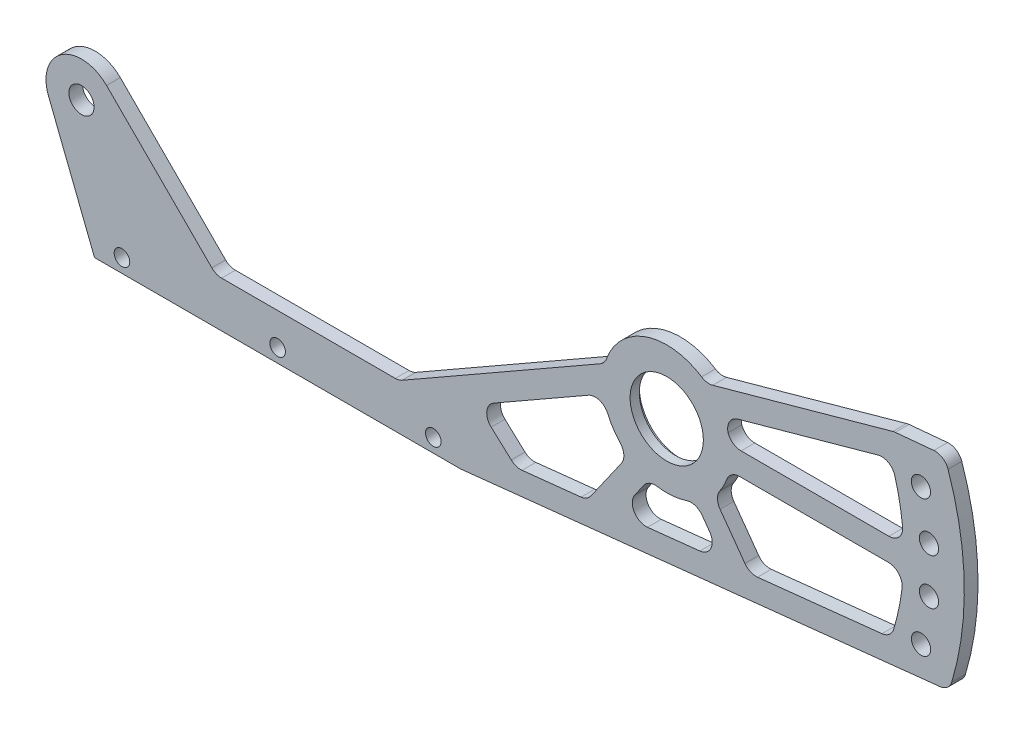
SolidWorks part; units mm, degrees
ref_plane "Спереди" through (0, 0, 0) normal (0, 0, 1) x (1, 0, 0)
ref_plane "Сверху" through (0, 0, 0) normal (0, 1, 0) x (1, 0, 0)
ref_plane "Справа" through (0, 0, 0) normal (1, 0, 0) x (0, 0, -1)
sketch "Эскиз1" plane through (0, 0, 0) normal (0, 0, 1) x (1, 0, 0)
  line L0 (0, 0) -> (80, 0)
  line L1 (80, 0) -> (186.6474, 11.3941)
  line L3 (185.6418, 55.4002) -> (29.8179, 40.9591)
  line L4 (29.8179, 40.9591) -> (0, 40.9591)
  line L5 (0, 40.9591) -> (0, 0)
  line L6 (125, 71.1667) -> (125, -25.6191) construction
  line L7 (154.8278, 32) -> (80, 32) construction
  circle A0 centre (125, 32) radius 8
  arc A1 (186.6474, 11.3941) -> (185.6418, 55.4002) centre (125, 32) ccw
  dimension "D4" = 16
  dimension "D3" = 130
  dimension "D1" = 80
  dimension "D2" = 45
extrude "Бобышка-Вытянуть1" add sketch "Эскиз1" along normal blind 3
sketch "Эскиз2" plane through (0, 0, 3) normal (0, 0, 1) x (1, 0, 0)
  line L0 (-2.7509, 3) -> (78.5336, 3) construction
  line L1 (0, 0) -> (80, 0) construction
  line L2 (6, 6.1653) -> (6, -1.4851) construction
  line L4 (74, 6.1653) -> (74, -1.4851) construction
  line L5 (0, 40.9591) -> (0, 0) construction
  line L6 (40, 0) -> (40, 7.0416) construction
  dimension "D1" = 3
  dimension "D2" = 6
  dimension "D4" = 6
hole_wizard "Отверстие с зазором M31" positions "Эскиз4" profile "Эскиз3" hole size "M3" standard "Ansi Metric" end condition through all
sketch "Эскиз4" plane through (0, 0, 3) normal (0, 0, 1) x (1, 0, 0)
  line L0 (-2.7509, 3) -> (78.5336, 3) construction
  line L1 (6, 6.1653) -> (6, -1.4851) construction
  line L3 (74, 6.1653) -> (74, -1.4851) construction
  line L4 (40, 0) -> (40, 7.0416) construction
  point P0 (6, 3)
  point P6 (40, 3)
  point P10 (74, 3)
sketch "Эскиз3" plane through (6, 3, 3) normal (1, 0, 0) x (0, -1, 0)
  line L0 (0, 0) -> (0, 3)
  line L1 (0, 3) -> (1.7, 3)
  line L2 (1.7, 3) -> (1.7, 0)
  line L5 (1.7, 0) -> (0, 0)
  line L11 (0, -6.35) -> (0, 107.95) construction
  dimension "Диаметр сквозного отверстия" = 3.4
  dimension "Глубина сквозного отверстия" = 3
sketch "Эскиз5" plane through (0, 0, 3) normal (0, 0, 1) x (1, 0, 0)
  line L0 (-10.0586, 25.5565) -> (0, 0)
  line L1 (0, 0) -> (0, 21.1867)
  circle A0 centre (-2.847, 28.3948) radius 2.75
  arc A1 (0, 21.1867) -> (-10.0586, 25.5565) centre (-2.847, 28.3948) ccw
  circle A3 centre (-2.847, 28.3948) radius 7.75 construction
  point P7 (4.903, 28.3948)
  dimension "D1" = 5.5
  dimension "D2" = 5
extrude "Бобышка-Вытянуть2" add sketch "Эскиз5" against normal up to surface (3 mm away) up to face at (7.7, 3, 0)
sketch "Эскиз6" plane through (0, 0, 3) normal (0, 0, 1) x (1, 0, 0)
  line L0 (-10.4862, 10) -> (81.8154, 10) construction
  line L1 (0, 0) -> (80, 0) construction
  line L2 (2.633, 33.8749) -> (26.5079, 10)
  line L3 (26.5079, 10) -> (66.5079, 10)
  line L4 (66.5079, 10) -> (104.3768, 47.8689)
  line L5 (185.6418, 55.4002) -> (29.8179, 40.9591) construction
  line L6 (104.3768, 47.8689) -> (29.8179, 40.9591)
  line L7 (29.8179, 40.9591) -> (0, 40.9591)
  line L8 (0, 40.9591) -> (0, 35.6029)
  line L9 (0.7482, 30) -> (105.8715, 30) construction
  arc A0 (0, 35.6029) -> (2.633, 33.8749) centre (-2.847, 28.3948) cw
  dimension "D2" = 20
  dimension "D4" = 45
  dimension "D3" = 45
  dimension "D1" = 10
  dimension "D5" = 40
extrude "Вырез-Вытянуть1" cut sketch "Эскиз6" against normal through all
sketch "Эскиз7" plane through (0, 0, 3) normal (0, 0, 1) x (1, 0, 0)
  line L0 (125, 32) -> (180.5279, 46.9298) construction
  line L1 (125, 32) -> (182.2769, 37.0606) construction
  line L2 (125, 32) -> (182.2855, 27.0377) construction
  line L3 (125, 32) -> (180.5535, 17.1656) construction
  circle A0 centre (125, 32) radius 57.5 construction
  dimension "D1" = 115
  dimension "D2" = 10
  dimension "D3" = 10
  dimension "D4" = 10
hole_wizard "Отверстие обработанное метчиком M5x0.81" positions "Эскиз9" profile "Эскиз8" tap size "M5x0.8" standard "Ansi Metric" end condition through all
sketch "Эскиз9" plane through (0, 0, 3) normal (0, 0, 1) x (1, 0, 0)
  point P0 (180.5279, 46.9298)
  point P3 (182.2769, 37.0606)
  point P6 (182.2855, 27.0377)
  point P9 (180.5535, 17.1656)
sketch "Эскиз8" plane through (180.5279, 46.9298, 3) normal (1, 0, 0) x (0, -1, 0)
  line L0 (0, 0) -> (0, 3)
  line L1 (0, 3) -> (2.1, 3)
  line L2 (2.1, 3) -> (2.1, 0)
  line L5 (2.1, 0) -> (0, 0)
  line L11 (0, -6.35) -> (0, 107.95) construction
  dimension "Диаметр проходного сверла" = 4.2
  dimension "Глубина проходного сверла" = 3
cosmetic thread "Отверстие резьбы1" parameters "D2"=5
cosmetic thread "Отверстие резьбы2" parameters "D2"=5
cosmetic thread "Отверстие резьбы3" parameters "D2"=5
cosmetic thread "Отверстие резьбы4" parameters "D2"=5
sketch "Эскиз10" plane through (0, 0, 3) normal (0, 0, 1) x (1, 0, 0)
  line L0 (66.5079, 10) -> (111.5092, 35.7414)
  line L1 (133.6695, 42.9927) -> (174.6526, 54.3818)
  line L2 (185.6418, 55.4002) -> (104.3768, 47.8689) construction
  line L3 (66.5079, 10) -> (104.3768, 47.8689)
  line L4 (104.3768, 47.8689) -> (174.6526, 54.3818)
  arc A0 (133.6695, 42.9927) -> (111.5092, 35.7414) centre (125, 32) ccw
  dimension "D1" = 28
extrude "Вырез-Вытянуть2" cut sketch "Эскиз10" against normal through all
sketch "Эскиз11" plane through (0, 0, 3) normal (0, 0, 1) x (1, 0, 0)
  line L0 (92.0344, 6.3142) -> (107.6302, 7.9804)
  line L1 (173.9308, 48.9917) -> (137.2401, 38.7955)
  line L2 (83.6238, 14.0303) -> (111.1755, 29.7903)
  line L3 (133.6695, 42.9927) -> (174.6526, 54.3818) construction
  line L4 (80, 0) -> (186.6474, 11.3941) construction
  line L5 (66.5079, 10) -> (111.5092, 35.7414) construction
  line L6 (83.6238, 14.0303) -> (92.0344, 6.3142)
  line L7 (116.6083, 20.7938) -> (107.6302, 7.9804)
  line L8 (121.1368, 18.5436) -> (114.2295, 8.6855)
  line L9 (125, 32) -> (104.4053, 2.6074) construction
  line L10 (131.3501, 19.523) -> (137.3788, 11.1587)
  line L11 (125, 32) -> (150.9131, -3.9523) construction
  line L12 (143.1015, 11.7701) -> (173.9508, 15.0661)
  line L13 (135.3307, 22.5514) -> (143.1015, 11.7701)
  line L14 (138.8492, 34.0496) -> (176.7565, 34.0496)
  line L15 (138.6856, 29.0496) -> (176.713, 29.0496)
  line L16 (125, 32) -> (176.7971, 32) construction
  line L17 (114.2295, 8.6855) -> (137.3788, 11.1587)
  arc A0 (138.8492, 34.0496) -> (137.2401, 38.7955) centre (125, 32) ccw
  arc A1 (133.6695, 42.9927) -> (111.5092, 35.7414) centre (125, 32) ccw construction
  arc A2 (173.9508, 15.0661) -> (176.713, 29.0496) centre (125, 32) ccw
  arc A3 (135.3307, 22.5514) -> (138.6856, 29.0496) centre (125, 32) ccw
  arc A4 (121.1368, 18.5436) -> (131.3501, 19.523) centre (125, 32) ccw
  arc A5 (111.1755, 29.7903) -> (116.6083, 20.7938) centre (125, 32) ccw
  arc A6 (176.7565, 34.0496) -> (173.9308, 48.9917) centre (125, 32) ccw
  dimension "D1" = 5
  dimension "D2" = 5
  dimension "D3" = 5
  dimension "D4" = 5
  dimension "D5" = 5
  dimension "D6" = 5
extrude "Вырез-Вытянуть3" cut sketch "Эскиз11" against normal through all
fillet "Скругление1" radius 3 25 edges at (138.8492, 34.0496, 1.5) (173.9308, 48.9917, 1.5) (176.713, 29.0496, 1.5) (143.1015, 11.7701, 1.5) (83.6238, 14.0303, 1.5) (92.0344, 6.3142, 1.5) (114.2295, 8.6855, 1.5) (131.3501, 19.523, 1.5) (121.1368, 18.5436, 1.5) (137.2401, 38.7955, 1.5) (135.3307, 22.5514, 1.5) (138.6856, 29.0496, 1.5) (173.9508, 15.0661, 1.5) (176.7565, 34.0496, 1.5) (107.6302, 7.9804, 1.5) (137.3788, 11.1587, 1.5) (116.6083, 20.7938, 1.5) (111.1755, 29.7903, 1.5) (66.5079, 10, 1.5) (26.5079, 10, 1.5) (186.6474, 11.3941, 1.5) (111.5092, 35.7414, 1.5) (133.6695, 42.9927, 1.5) (185.6418, 55.4002, 1.5) (174.6526, 54.3818, 1.5)
sketch "Эскиз12" plane through (0, 0, 0) normal (0, 0, 1) x (1, 0, 0)
  circle A0 centre (125, 32) radius 9
  dimension "D1" = 18
extrude "Вырез-Вытянуть4" cut sketch "Эскиз12" along normal blind 1
equation "\"D3@Эскиз7\"=\"D2@Эскиз7\""
equation "\"D4@Эскиз7\"=\"D2@Эскиз7\""
